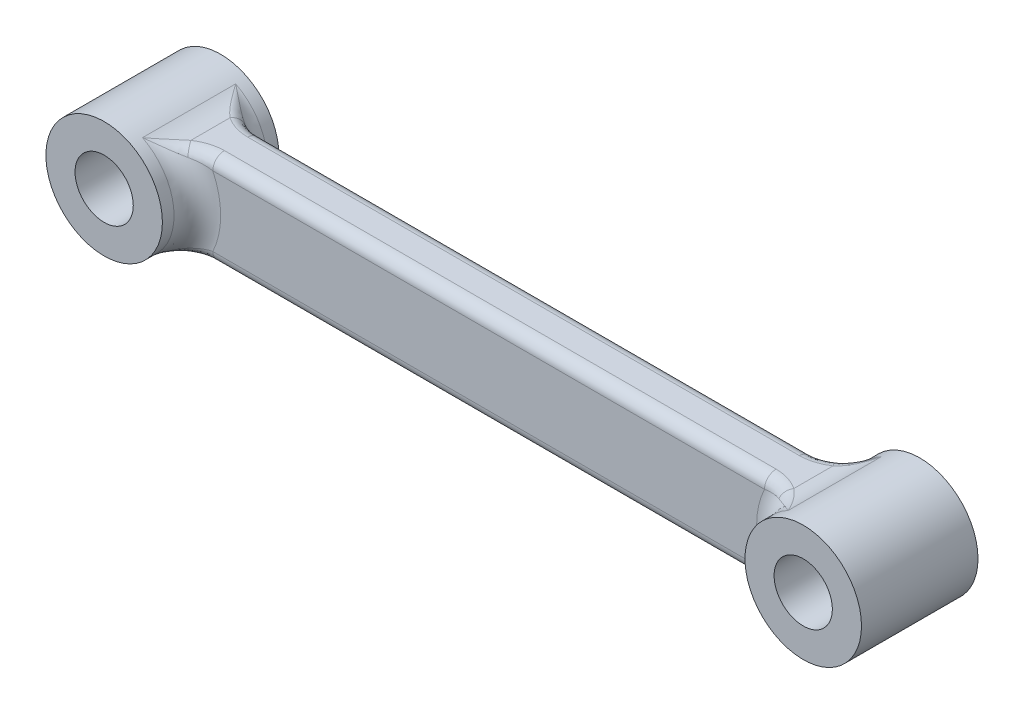
SolidWorks part; units mm, degrees
ref_plane "Front Plane" through (0, 0, 0) normal (0, 0, 1) x (1, 0, 0)
ref_plane "Top Plane" through (0, 0, 0) normal (0, 1, 0) x (1, 0, 0)
ref_plane "Right Plane" through (0, 0, 0) normal (1, 0, 0) x (0, 0, -1)
sketch "Sketch1" plane through (0, 0, 0) normal (0, 0, 1) x (1, 0, 0)
  circle A0 centre (0, 0) radius 5
  circle A1 centre (0, 0) radius 2.5
  circle A2 centre (60, 0) radius 5
  circle A3 centre (60, 0) radius 2.5
  point P7 (59.5165, 7.6017)
  dimension "D1" = 10
  dimension "D2" = 5
  dimension "D3" = 60
extrude "Boss-Extrude1" add sketch "Sketch1" along normal mid plane 10
sketch "Sketch2" plane through (0, 0, 0) normal (0, 0, 1) x (1, 0, 0)
  line L2 (3, 4) -> (57, 4)
  line L3 (3, -4) -> (57, -4)
  circle A0 centre (60, 0) radius 5 construction
  circle A1 centre (0, 0) radius 5 construction
  circle A2 centre (60, 0) radius 5
  circle A3 centre (0, 0) radius 5
  arc A4 (3, -4) -> (3, 4) centre (0, 0) ccw
  arc A5 (57, 4) -> (57, -4) centre (60, 0) ccw
  point P3 (0, 0)
  point P6 (60, 0)
  point P14 (0, 0)
  dimension "D1" = 8
  dimension "D2" = 4
extrude "Boss-Extrude2" add sketch "Sketch2" along normal mid plane 4 contours A3 L3 A2 L2 region at (30, 0, 0)
fillet "Fillet1" radius 2 4 edges at (5, 0, -2) (55, 0, -2) (55, 0, 2) (5, 0, 2)
fillet "Fillet2" radius 4 4 edges at (3, 4, 0) (57, 4, 0) (3, -4, 0) (57, -4, 0)
fillet "Fillet3" radius 1 20 edges at (2.9732, 4.1688, 3.3163) (5.0296, 4, 2.0841) (57.0268, 4.1688, 3.3163) (55.2554, 4, 2.1645) (2.9732, -4.1688, 3.3163) (4.7446, -4, 2.1645) (57.0268, -4.1688, 3.3163) (54.9704, -4, 2.0841) (2.9732, 4.1688, -3.3163) (4.7446, 4, -2.1645) (57.0268, 4.1688, -3.3163) (54.9704, 4, -2.0841) (2.9732, -4.1688, -3.3163) (5.0296, -4, -2.0841) (57.0268, -4.1688, -3.3163) (55.2554, -4, -2.1645) (30, 4, 2) (30, -4, 2) (30, 4, -2) (30, -4, -2)
